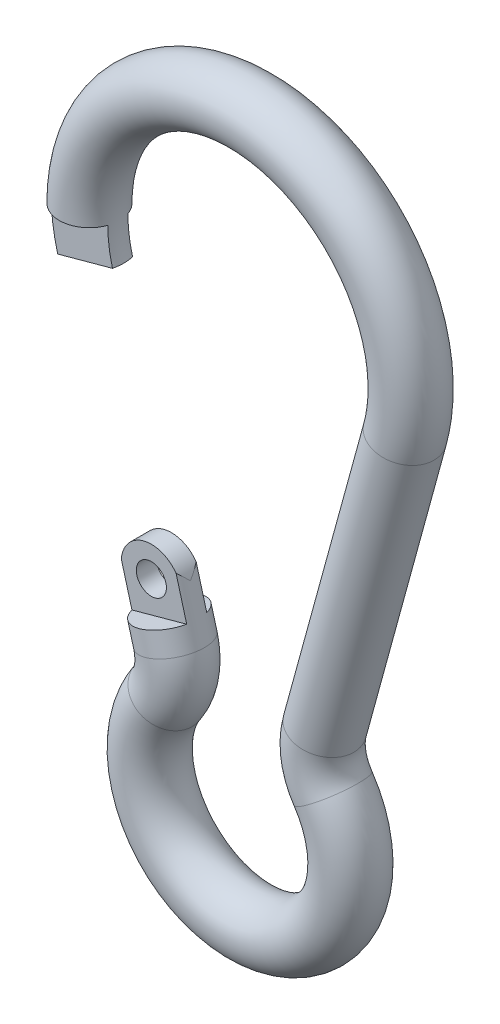
SolidWorks part; units mm, degrees
ref_plane "Front Plane" through (0, 0, 0) normal (0, 0, 1) x (1, 0, 0)
ref_plane "Top Plane" through (0, 0, 0) normal (0, 1, 0) x (1, 0, 0)
ref_plane "Right Plane" through (0, 0, 0) normal (1, 0, 0) x (0, 0, -1)
sketch "Sketch1" plane through (0, 0, 0) normal (0, 0, 1) x (1, 0, 0)
  line L0 (0, 0) -> (0, 55.88) construction
  line L1 (15.9242, 51.5211) -> (5.7761, 14.4477)
  line L2 (-15.9242, 51.5211) -> (-5.7761, 14.4477)
  arc A0 (-7.3502, 5.0006) -> (7.3502, 5.0006) centre (0, 0) ccw
  arc A1 (15.9242, 51.5211) -> (-15.9242, 51.5211) centre (0, 55.88) ccw
  arc A2 (5.7761, 14.4477) -> (7.3502, 5.0006) centre (16.8005, 11.43) ccw
  arc A3 (-5.7761, 14.4477) -> (-7.3502, 5.0006) centre (-16.8005, 11.43) cw
  point P1 (0, 0)
  point P7 (0, 0)
  dimension "D1" = 17.78
  dimension "D2" = 33.02
  dimension "D4" = 22.86
  dimension "D3" = 55.88
  dimension "D5" = 11.43
ref_plane "Plane1" through (15.9242, 51.5211, 0) normal (-0.264, -0.9645, 0) x (-0.9645, 0.264, 0)
sketch "Sketch2" plane through (15.9242, 51.5211, 0) normal (-0.264, -0.9645, 0) x (-0.9645, 0.264, 0)
  line L0 (0, 0) -> (0, -7.1624) construction
  circle A0 centre (-3.81, 0) radius 3.81
  point P4 (0, 0)
  dimension "D1" = 7.62
sweep "Sweep1" add profiles "Sketch2" path "Sketch1"
ref_plane "Plane2" through (0, 0, 25) normal (0, 0, 1) x (1, 0, 0)
sketch "Sketch4" plane through (0, 0, 25) normal (0, 0, 1) x (1, 0, 0)
  line L0 (-15.9242, 51.5211) -> (-23.2738, 49.5092)
  line L1 (-23.2738, 49.5092) -> (-15.8972, 22.5606)
  line L2 (-23.2738, 49.5092) -> (-13.1257, 12.4359) construction
  line L3 (-15.8972, 22.5606) -> (-8.5475, 24.5724)
  line L4 (-5.7761, 14.4477) -> (-15.9242, 51.5211) construction
  line L5 (-8.5475, 24.5724) -> (-15.9242, 51.5211)
  dimension "D1" = 27.94
extrude "Cut-Extrude2" cut sketch "Sketch4" against normal through all both and the other way through all
sketch "Sketch5" plane through (0, 0, 25) normal (0, 0, 1) x (1, 0, 0)
  line L0 (-16.51, 55.88) -> (-24.13, 55.88)
  line L1 (-23.2738, 49.5092) -> (-15.9242, 51.5211)
  line L2 (-23.2738, 49.5092) -> (-15.9242, 51.5211) construction
  arc A0 (23.2738, 49.5092) -> (-23.2738, 49.5092) centre (0, 55.88) ccw construction
  arc A2 (-24.13, 55.88) -> (-23.2738, 49.5092) centre (0, 55.88) ccw
  arc A3 (-16.51, 55.88) -> (-15.9242, 51.5211) centre (0, 55.88) ccw
extrude "Cut-Extrude3" cut sketch "Sketch5" against normal offset from surface 1.27 and the other way through all up to plane "Front Plane"
mirror "Mirror1" about plane through (0, 0, 0) normal (0, 0, 1) of "Cut-Extrude3"
sketch "Sketch7" plane through (0, 0, 25) normal (0, 0, 1) x (1, 0, 0)
  line L0 (-14.8912, 18.8858) -> (-13.8853, 15.211)
  line L1 (-13.8853, 15.211) -> (-6.5357, 17.2228)
  line L2 (-6.5357, 17.2228) -> (-7.5416, 20.8976)
  line L3 (-15.8972, 22.5606) -> (-13.1257, 12.4359) construction
  line L5 (-23.0636, 49.5668) -> (-16.1344, 51.4635) construction
  line L6 (-14.8912, 18.8858) -> (-15.8972, 22.5606)
  line L7 (-15.8972, 22.5606) -> (-8.5475, 24.5724)
  line L8 (-7.5416, 20.8976) -> (-8.5475, 24.5724)
  circle A0 centre (-11.2164, 19.8917) radius 1.905
  arc A1 (-7.5416, 20.8976) -> (-14.8912, 18.8858) centre (-11.2164, 19.8917) ccw
  dimension "D1" = 3.81
  dimension "D2" = 31.75
  dimension "D3" = 3.81
extrude "Cut-Extrude4" cut sketch "Sketch7" against normal through all both and the other way through all contours A1 L7 L6 | A1 L8 L7 | A0 region at (-14.8516, 21.9645, 25) region at (-9.1437, 23.5269, 25)
extrude "Cut-Extrude5" cut sketch "Sketch7<3>" against normal offset from surface 1.27 and the other way through all contours L2 A1 L0 L1 A0 region at (-14.4219, 21.7194, 25) up to plane "Front Plane"
sketch "Sketch7<3>" plane through (0, 0, 25) normal (0, 0, 1) x (1, 0, 0) same geometry as "Sketch7"
mirror "Mirror2" about plane through (0, 0, 0) normal (0, 0, 1) of "Cut-Extrude5"
